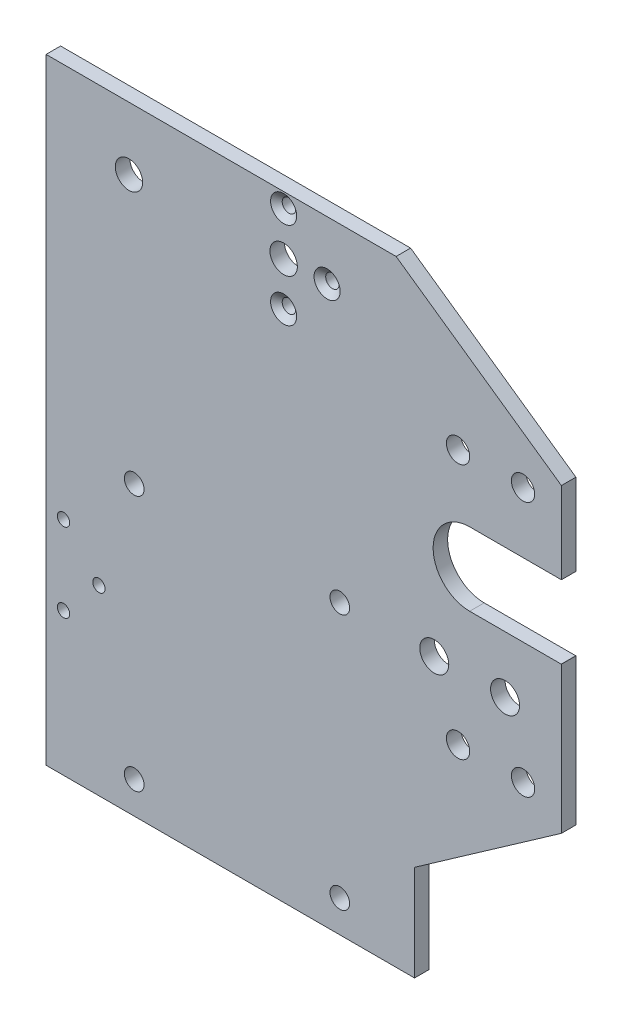
SolidWorks part; units mm, degrees
note: '?' marks a value the reader was unsure of.
material "5052-H32"
ref_plane "Front" through (0, 0, 0) normal (0, 0, 1) x (1, 0, 0)
ref_plane "Top" through (0, 0, 0) normal (0, 1, 0) x (1, 0, 0)
ref_plane "Right" through (0, 0, 0) normal (1, 0, 0) x (0, 0, -1)
ref_axis "side-side" through (80.9, 0, 0) along (-1, 0, 0)?
ref_axis "up-down" through (0, 50, 0) along (0, -1, 0)?
ref_axis "front-back" through (0, 0, -80.9) along (0, 0, 1)?
sketch3d "3DSketch1"
  line L1 (-36.063, 17.578, 17.275) -> (-36.063, -7.822, 17.275)
  line L3 (-32.888, 17.578, 14.1) -> (-32.888, -7.822, 14.1)
  line L8 (27.5, 33, 11.8) -> (-27.5, 33, 11.8)
  line L9 (-27.5, 33, 11.8) -> (-27.5, -33, 11.8)
  line L10 (-27.5, -33, 11.8) -> (27.5, -33, 11.8)
  line L11 (27.5, -33, 11.8) -> (27.5, 33, 11.8)
  line L20 (12.852, 79.3579, 11.8) -> (17.9378, 74.2721, 11.8)
  line L21 (17.9378, 74.2721, 11.8) -> (20.7662, 74.2721, 11.8)
  line L22 (20.7662, 74.2721, 11.8) -> (32.0799, 85.5858, 11.8)
  line L23 (32.0799, 85.5858, 11.8) -> (32.0799, 88.4142, 11.8)
  line L24 (32.0799, 88.4142, 11.8) -> (20.7662, 99.7279, 11.8)
  line L25 (20.7662, 99.7279, 11.8) -> (17.9378, 99.7279, 11.8)
  line L26 (17.9378, 99.7279, 11.8) -> (12.852, 94.6421, 11.8)
  line L27 (12.852, 94.6421, 11.8) -> (12.852, 79.3579, 11.8)
  circle A1 centre (-13.356, 28, 11.8) radius 2.025
  circle A2 centre (-51.308, -14.6, 8.382) radius 19.2253 construction
  circle A3 centre (-55.372, 23.5, 14.3256) radius 19.2278 construction
  circle A4 centre (60.066, 41.6513, -10.821) radius 18.5
  circle A5 centre (67.816, 55.0747, -10.821) radius 1.25
  circle A7 centre (52.316, 28.2279, -14.321) radius 1.25
  circle A8 centre (-22.5, 28, 11.8) radius 2.025
  circle A9 centre (22.5, 28, 11.8) radius 2.025
  circle A10 centre (22.5, -28, 11.8) radius 2.025
  circle A11 centre (-22.5, -28, 11.8) radius 2.025
  circle A13 centre (67.816, 28.2279, -14.321) radius 1.25
  circle A15 centre (44.566, 41.6513, -10.821) radius 1.25
  circle A18 centre (75.566, 41.6513, -10.821) radius 1.25
  circle A20 centre (52.316, 55.0747, -10.821) radius 1.25
  circle A21 centre (31.644, -28, 11.8) radius 2.025
  circle A22 centre (19.352, 96.5191, 11.8) radius 1.1303
  circle A24 centre (19.352, 77.4809, 11.8) radius 1.1303
  circle A26 centre (22.352, 87, 23.5) radius 6
  circle A27 centre (22.352, 87, 23.5) radius 3
  circle A28 centre (28.8711, 87, 11.8) radius 1.1303
  circle A29 centre (22.352, 87, 31.5) radius 3
  circle A31 centre (22.352, 87, 31.5) radius 3.8268
  circle A33 centre (22.352, 87, 30.85) radius 4.5
  arc A40 (-37.9129, 67.2371, 9.4869) -> (-37.9129, 62.5513, 9.4869) centre (-46.0199, 64.8942, 9.4869) ccw
  arc A41 (-37.9129, 62.5513, 9.4869) -> (-32.1541, 62.5513, 9.4869) centre (-35.0335, 61.7192, 9.4869) ccw
  arc A42 (-32.1541, 62.5513, 9.4869) -> (-32.1541, 67.2371, 9.4869) centre (-24.0471, 64.8942, 9.4869) ccw
  arc A43 (-32.1541, 67.2371, 9.4869) -> (-37.9129, 67.2371, 9.4869) centre (-35.0335, 68.0692, 9.4869) ccw
  point P16 (31.644, -28, 13.825)
  point P21 (-22.5, 28, 13.825)
  point P23 (22.5, 28, 13.825)
  point P25 (22.5, -28, 13.825)
  point P27 (-22.5, -28, 13.825)
  point P33 (44.566, 41.6513, -12.071)
  point P37 (19.352, 96.5191, 12.9303)
  point P42 (19.352, 77.4809, 12.9303)
  point P48 (28.8711, 87, 12.9303)
  point P50 (-51.308, -14.6, 27.6073)
  point P51 (-13.356, 28, 13.825)
  point P58 (-55.372, 23.5, -4.9022)
  point P60 (22.352, 87, 17.5)
  point P62 (22.352, 87, 26.5)
  point P67 (22.352, 87, 28.5)
  point P71 (22.352, 87, 35.3268)
  point P76 (22.352, 87, 35.35)
  point P78 (-46.0199, 64.8942, 1.0482)
  point P80 (-35.0335, 61.7192, 12.4841)
  point P81 (-24.0471, 64.8942, 1.0482)
  point P83 (-35.0335, 68.0692, 12.4841)
  point P85 (52.316, 55.0747, -12.071)
  point P100 (60.066, 41.6513, -29.321)
  point P103 (67.816, 55.0747, -12.071)
  point P116 (52.316, 28.2279, -13.071)
  point P128 (67.816, 28.2279, -13.071)
  point P133 (75.566, 41.6513, -12.071)
sketch "Sketch1" plane through (0, 0, 0) normal (0, 1, 0) x (1, 0, 0)
  line L0 (-32.638, -14.975) -> (80.144, -14.975)
  line L1 (49.144, -9.3) -> (49.144, -0.5) construction
  line L7 (80.144, -14.975) -> (80.144, -11.8)
  line L8 (80.144, -11.8) -> (-32.638, -11.8)
  line L9 (-32.638, -11.8) -> (-32.638, -14.975)
  line L10 (27.5, -11.8) -> (-27.5, -11.8) construction
  line L11 (0, -50) -> (0, 50) construction
  line L13 (-38.0307, -1.4658) -> (-38.0307, -18.0357) construction
  dimension "D1" = 3.175
  dimension "D2" = 31
  dimension "D3" = 0.25
  dimension "D5" = 5.138
  dimension "D6" = 80.144
extrude "Boss-Extrude1" add sketch "Sketch1" along normal blind 99.75 and the other way blind 35
sketch "Sketch2" plane through (0, 0, 0) normal (0, 0, 1) x (1, 0, 0)
  line L0 (60.066, 48.5504) -> (80.066, 48.5504) construction
  line L1 (48, -35) -> (80.144, -35)
  line L2 (48, -35) -> (48, -14.0202)
  line L3 (60.066, 56.5504) -> (80.066, 56.5504)
  line L4 (80.144, -35) -> (80.144, 8.4873)
  line L5 (43.9647, 99.75) -> (80.144, 74.417)
  line L6 (43.9647, 99.75) -> (80.144, 99.75)
  line L7 (60.066, 40.5504) -> (80.066, 40.5504)
  line L9 (80.144, 99.75) -> (80.144, 74.417)
  line L10 (80.144, 8.4873) -> (48, -14.0202)
  line L11 (0, -50) -> (0, 50) construction
  line L12 (-32.638, -35) -> (80.144, -35) construction
  line L13 (-32.638, 99.75) -> (80.144, 99.75) construction
  arc A0 (60.066, 56.5504) -> (60.066, 40.5504) centre (60.066, 48.5504) ccw
  arc A1 (80.066, 40.5504) -> (80.066, 56.5504) centre (80.066, 48.5504) ccw
  circle A2 centre (52.316, 28.127) radius 3.175
  circle A3 centre (67.816, 28.127) radius 3.175
  point P1 (70.066, 48.5504)
  dimension "D9" = 6.35
  dimension "D1" = 48
  dimension "D2" = 38.6
  dimension "D3" = 55
  dimension "D4" = 55
  dimension "D5" = 16
  dimension "D6" = 20
  dimension "D7" = 32.144
  dimension "D8" = 38.6866
  dimension "D10" = 43.9647
extrude "Cut-Extrude1" cut sketch "Sketch2" against normal through all and the other way through all
sketch "Sketch3" [suppressed] plane through (43.8, 0, 0) normal (1, 0, 0) x (0, 0, -1)
  line L0 (-11.8, -12.8411) -> (-14.1, -12.8411) construction
  line L1 (10.819, 98) -> (2.819, 98)
  line L2 (10.819, 98) -> (10.819, 71.012)
  line L3 (10.819, 71.012) -> (2.819, 71.012)
  line L4 (2.819, 98) -> (2.819, 71.012)
  line L5 (10.819, -35) -> (2.819, -35)
  line L6 (10.819, -35) -> (10.819, -12.8411)
  line L7 (10.819, -12.8411) -> (2.819, -12.8411)
  line L8 (2.819, -35) -> (2.819, -12.8411)
  dimension "D1" = 8
  dimension "D2" = 8
extrude "Cut-Extrude2" [suppressed] cut sketch "Sketch3" against normal blind 3
hole_wizard "M4 Clearance Hole1" positions "Sketch4" profile "Sketch5" hole size "M4" standard "ANSI Metric" end condition through all
sketch "Sketch4" plane through (0, 0, 14.975) normal (0, 0, 1) x (1, 0, 0)
  point P0 (-13.356, 28)
  point P3 (31.644, 28)
  point P6 (31.644, -28)
  point P9 (-13.356, -28)
sketch "Sketch5" plane through (-13.356, 28, 14.975) normal (1, 0, 0) x (0, -1, 0)
  line L0 (0, 0) -> (0, 3.175)
  line L1 (0, 3.175) -> (2.15, 3.175)
  line L2 (2.15, 3.175) -> (2.15, 0)
  line L5 (2.15, 0) -> (0, 0)
  line L11 (0, -6.35) -> (0, 107.95) construction
  dimension "Thru Hole Dia." = 4.3
  dimension "Thru Hole Depth" = 3.175
hole_wizard "CSK for #4 Flat Head Machine Screw (100)1" positions "Sketch6" profile "Sketch7" countersink size "#4" standard "ANSI Inch" end condition through all
sketch "Sketch6" plane through (0, 0, 14.975) normal (0, 0, 1) x (1, 0, 0)
  point P70 (19.352, 96.5191)
  point P73 (28.8711, 87)
  point P76 (19.352, 77.4809)
sketch "Sketch7" plane through (19.352, 96.5191, 14.975) normal (1, 0, 0) x (0, -1, 0)
  line L0 (0, 0) -> (0, 3.175)
  line L1 (0, 3.175) -> (1.4732, 3.175)
  line L2 (1.4732, 3.175) -> (1.4732, 1.1616)
  line L3 (1.4732, 1.1616) -> (2.8575, 0)
  line L5 (2.8575, 0) -> (0, 0)
  line L6 (-1.4732, 1.1616) -> (-2.8575, 0) construction
  line L11 (0, -6.35) -> (0, 107.95) construction
  dimension "Thru Hole Dia." = 2.9464
  dimension "Thru Hole Depth" = 3.175
  dimension "Near C'Sink Dia." = 5.715
  dimension "Near C'Sink Angle" = 100
sketch "Sketch8" plane through (0, 0, 14.975) normal (0, 0, 1) x (1, 0, 0)
  circle A1 centre (19.352, 87) radius 3
  dimension "D1" = 6
extrude "Cut-Extrude3" cut sketch "Sketch8" against normal blind 3.5
hole_wizard "5/16-18 Tapped Hole1" [suppressed] positions "Sketch9" profile "Sketch10" tap size "5/16-18" standard "ANSI Inch"
sketch "Sketch9" plane through (0, 0, 14.975) normal (0, 0, 1) x (1, 0, 0)
  point P0 (-12.7036, 77.5964)
sketch "Sketch10" plane through (-12.7036, 77.5964, 14.975) normal (1, 0, 0) x (0, -1, 0)
  line L0 (0, 0) -> (0, 3.175)
  line L1 (0, 3.175) -> (3.2639, 3.175)
  line L2 (3.2639, 3.175) -> (3.2639, 0)
  line L5 (3.2639, 0) -> (0, 0)
  line L11 (0, -6.35) -> (0, 107.95) construction
  dimension "Thread Major Dia." = 6.5278
  dimension "Thru Tap Drill Depth" = 3.175
hole_wizard "#6-32 Tapped Hole1" positions "Sketch12" profile "Sketch13" tap size "#6-32" standard "ANSI Inch" end condition through all
sketch "Sketch12" plane through (0, 0, 14.975) normal (0, 0, 1) x (1, 0, 0)
  point P0 (-28.824, -3.758)
  point P3 (-21.077, 4.878)
  point P6 (-28.824, 13.514)
sketch "Sketch13" plane through (-28.824, -3.758, 14.975) normal (1, 0, 0) x (0, -1, 0)
  line L0 (0, 0) -> (0, 3.175)
  line L1 (0, 3.175) -> (1.3525, 3.175)
  line L2 (1.3525, 3.175) -> (1.3525, 0)
  line L5 (1.3525, 0) -> (0, 0)
  line L11 (0, -6.35) -> (0, 107.95) construction
  dimension "Thread Major Dia." = 2.7051
  dimension "Thru Tap Drill Depth" = 3.175
hole_wizard "1/4-20 Tapped Hole1" positions "Sketch14" profile "Sketch15" tap size "1/4-20" standard "ANSI Inch" end condition through all
sketch "Sketch14" plane through (0, 0, 14.975) normal (0, 0, 1) x (1, 0, 0)
  point P0 (57.526, 13.97)
  point P3 (71.75, 13.97)
  point P6 (71.75, 69.85)
  point P9 (57.526, 69.85)
sketch "Sketch15" plane through (57.526, 13.97, 14.975) normal (1, 0, 0) x (0, -1, 0)
  line L0 (0, 0) -> (0, 3.175)
  line L1 (0, 3.175) -> (2.5527, 3.175)
  line L2 (2.5527, 3.175) -> (2.5527, 0)
  line L5 (2.5527, 0) -> (0, 0)
  line L11 (0, -6.35) -> (0, 107.95) construction
  dimension "Thread Major Dia." = 5.1054
  dimension "Thru Tap Drill Depth" = 3.175
sketch "Sketch16" plane through (0, 0, 14.975) normal (0, 0, 1) x (1, 0, 0)
  line L1 (-20.8561, -40) -> (-20.8561, 370.2) construction
  line L2 (-32.638, -35) -> (-32.638, 99.75) construction
  line L3 (-32.638, 99.75) -> (43.9647, 99.75) construction
  circle A0 centre (-14.5061, 86.034) radius 2.9972
  circle A1 centre (19.352, 87) radius 3 construction
  dimension "D1" = 6.35
  dimension "D2" = 33.8581
  dimension "D3" = 18.1319
  dimension "D5" = 5.9944
  dimension "D4" = 13.716
extrude "Cut-Extrude4" cut sketch "Sketch16" against normal through all
